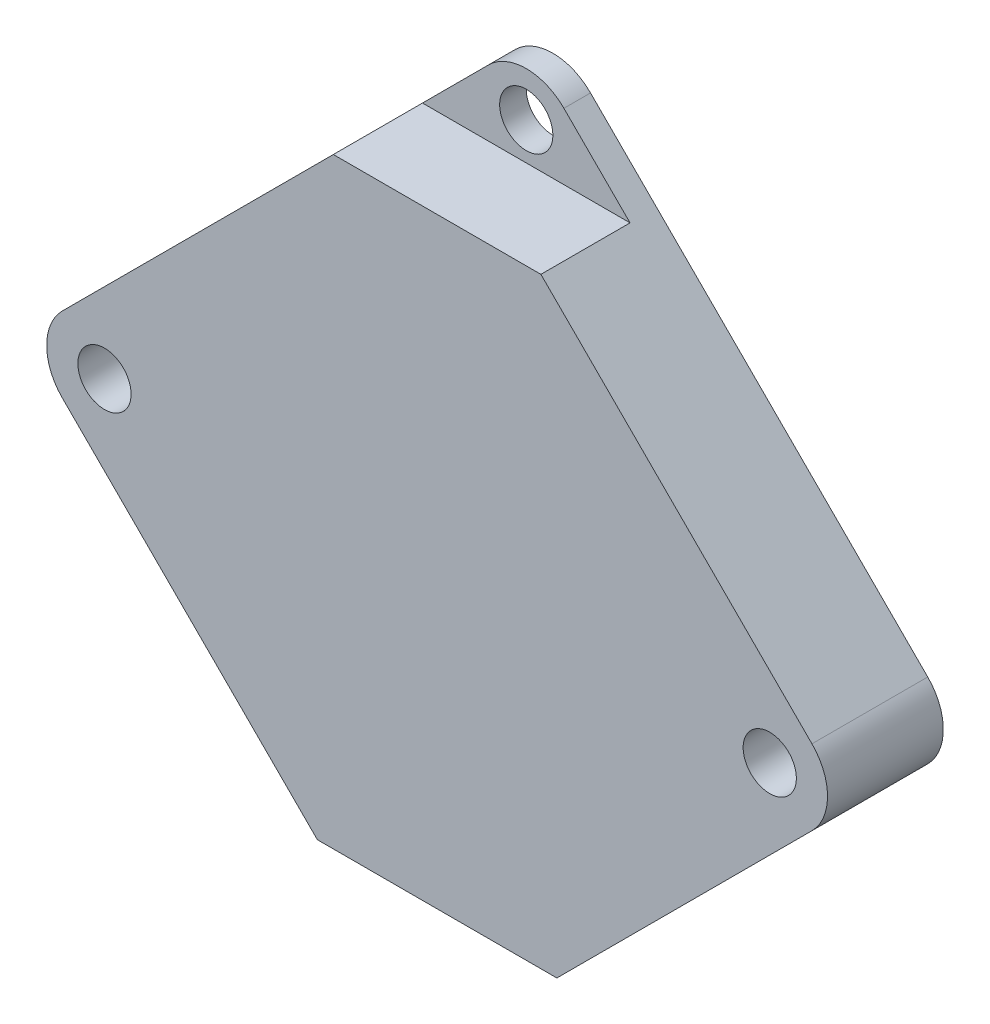
SolidWorks part; units mm, degrees
other "Markup1"
sketch "Sketch12" plane through (-14.6716, -11, 0) normal (-0.9917, -0.1032, -0.0761) x (-0.1011, 0.9944, -0.0314)
ref_plane "Front Plane" through (0, 0, 0) normal (0, 0, 1) x (1, 0, 0)
ref_plane "Top Plane" through (0, 0, 0) normal (0, 1, 0) x (1, 0, 0)
ref_plane "Right Plane" through (0, 0, 0) normal (1, 0, 0) x (0, 0, -1)
sketch "Sketch1" plane through (0, 0, 0) normal (0, 0, 1) x (1, 0, 0)
  line L0 (-12.5, 0) -> (12.5, 0) construction
  line L1 (0, 13) -> (0, 0) construction
  line L2 (0, 15.5) -> (-15.5, 0)
  line L3 (-15.5, 0) -> (0, -15.5)
  line L4 (0, -15.5) -> (15.5, 0)
  line L5 (15.5, 0) -> (0, 15.5)
  circle A0 centre (0, 0) radius 10
  circle A1 centre (12.5, 0) radius 1
  circle A2 centre (-12.5, 0) radius 1
  circle A3 centre (0, 13) radius 1
  circle A4 centre (0, 7) radius 4.1
  point P8 (10, 0)
  dimension "D1" = 20
  dimension "D2" = 2
  dimension "D3" = 2.5
  dimension "D4" = 2
  dimension "D5" = 7
  dimension "D6" = 8.2
  dimension "D7" = 13
  dimension "D9" = 3
  dimension "D10" = 3
extrude "Boss-Extrude1" add sketch "Sketch1" along normal blind 4.35 contours L5 L2 L3 L4
extrude "Cut-Extrude1" cut sketch "Sketch1<3>" along normal through all contours A2 | A1 | A3 region at (12.5, 0, 0) region at (-12.5, 0, 0)
sketch "Sketch1<3>" plane through (0, 0, 0) normal (0, 0, 1) x (1, 0, 0) same geometry as "Sketch1"
extrude "Cut-Extrude2" cut sketch "Sketch1<4>" along normal blind 2 contours A0 A4 | A4 A0 | A4 region at (0, -1.1865, 0) region at (0, 10.3338, 0)
sketch "Sketch1<4>" plane through (0, 0, 0) normal (0, 0, 1) x (1, 0, 0) same geometry as "Sketch1"
fillet "Fillet1" radius 2 4 edges at (0, -15.5, 2.175) (-15.5, 0, 2.175) (0, 15.5, 2.175) (15.5, 0, 2.175)
sketch "Sketch2" plane through (0, 0, 0) normal (0, 0, -1) x (-1, 0, 0)
  line L3 (-4.5, -11) -> (4.5, -11)
  line L5 (-1.4142, -14.0858) -> (-14.0858, -1.4142) construction
  line L6 (14.0858, -1.4142) -> (1.4142, -14.0858) construction
  line L11 (-14.0858, -1.4142) -> (-1.4142, -14.0858)
  line L12 (1.4142, -14.0858) -> (14.0858, -1.4142)
  line L13 (14.0858, 1.4142) -> (1.4142, 14.0858)
  line L14 (-1.4142, 14.0858) -> (-14.0858, 1.4142)
  line L15 (-4.5, -11) -> (-1.4142, -14.0858)
  line L16 (1.4142, -14.0858) -> (4.5, -11)
  arc A1 (-3.2933, 9.4421) -> (3.2933, 9.4421) centre (0, 0) ccw construction
  arc A6 (-1.4142, -14.0858) -> (1.4142, -14.0858) centre (0, -12.6716) ccw
  arc A7 (14.0858, -1.4142) -> (14.0858, 1.4142) centre (12.6716, 0) ccw
  arc A8 (1.4142, 14.0858) -> (-1.4142, 14.0858) centre (0, 12.6716) ccw
  arc A9 (-14.0858, 1.4142) -> (-14.0858, -1.4142) centre (-12.6716, 0) ccw
  arc A10 (-1.4142, -14.0858) -> (1.4142, -14.0858) centre (0, -12.6716) ccw
  arc A12 (1.4142, 14.0858) -> (-1.4142, 14.0858) centre (0, 12.6716) ccw
  point P6 (0, -10)
  line M15 (-14.0858, -1.4142) -> (-1.4142, -14.0858)
  arc M16 (-1.4142, -14.0858) -> (1.4142, -14.0858) centre (0, -12.6716) ccw
  line M17 (1.4142, -14.0858) -> (14.0858, -1.4142)
  dimension "D1" = 1
  dimension "D2" = 0
extrude "Cut-Extrude3" cut sketch "Sketch2" against normal through all contours L3 M15 M16 M17 region at (0, -12.3952, 0)
sketch "Sketch4" plane through (0, -11, 0) normal (0, -1, 0) x (1, 0, 0)
  line L2 (-1, 2) -> (1, 2) construction
  line L3 (-1, 2.7) -> (1, 2.7)
  line L4 (-1, 1.3) -> (1, 1.3)
  line L6 (0, 1.3) -> (0, 0)
  line L7 (4.5, 0) -> (-4.5, 0) construction
  arc A1 (-1, 2.7) -> (-1, 1.3) centre (-1, 2) ccw
  arc A2 (1, 1.3) -> (1, 2.7) centre (1, 2) ccw
  point P8 (0, 2)
  dimension "D2" = 1.3
  dimension "D1" = 2
  dimension "D3" = 1.4
extrude "Cut-Extrude4" cut sketch "Sketch4" against normal blind 21.2 contours L4 A2 L3 A1 region at (0, -11, 2)
sketch "Sketch10" plane through (0, 0, 4.35) normal (0, 0, 1) x (1, 0, 0)
  line L1 (-18.2088, 15.6928) -> (16.7269, 15.6928)
  line L2 (-18.2088, 15.6928) -> (-18.2088, -13.9696)
  line L3 (-18.2088, -13.9696) -> (16.7269, -13.9696)
  line L4 (16.7269, 15.6928) -> (16.7269, -13.9696)
sketch "Sketch11" plane through (0, 0, 4.35) normal (0, 0, 1) x (1, 0, 0)
  line L0 (-3.9, 11.6) -> (3.9, 11.6)
  line L1 (-1.4142, 14.0858) -> (-14.0858, 1.4142) construction
  line L2 (14.0858, 1.4142) -> (1.4142, 14.0858) construction
  line L3 (3.9, 11.6) -> (0, 15.5)
  line L4 (0, 15.5) -> (-3.9, 11.6)
  line L5 (0, 0) -> (0, 22.7627) construction
  dimension "D1" = 3.9
extrude "Cut-Extrude5" cut sketch "Sketch11" against normal offset from surface (3.35 mm away) 1 up to face at (1, 13, 0)
